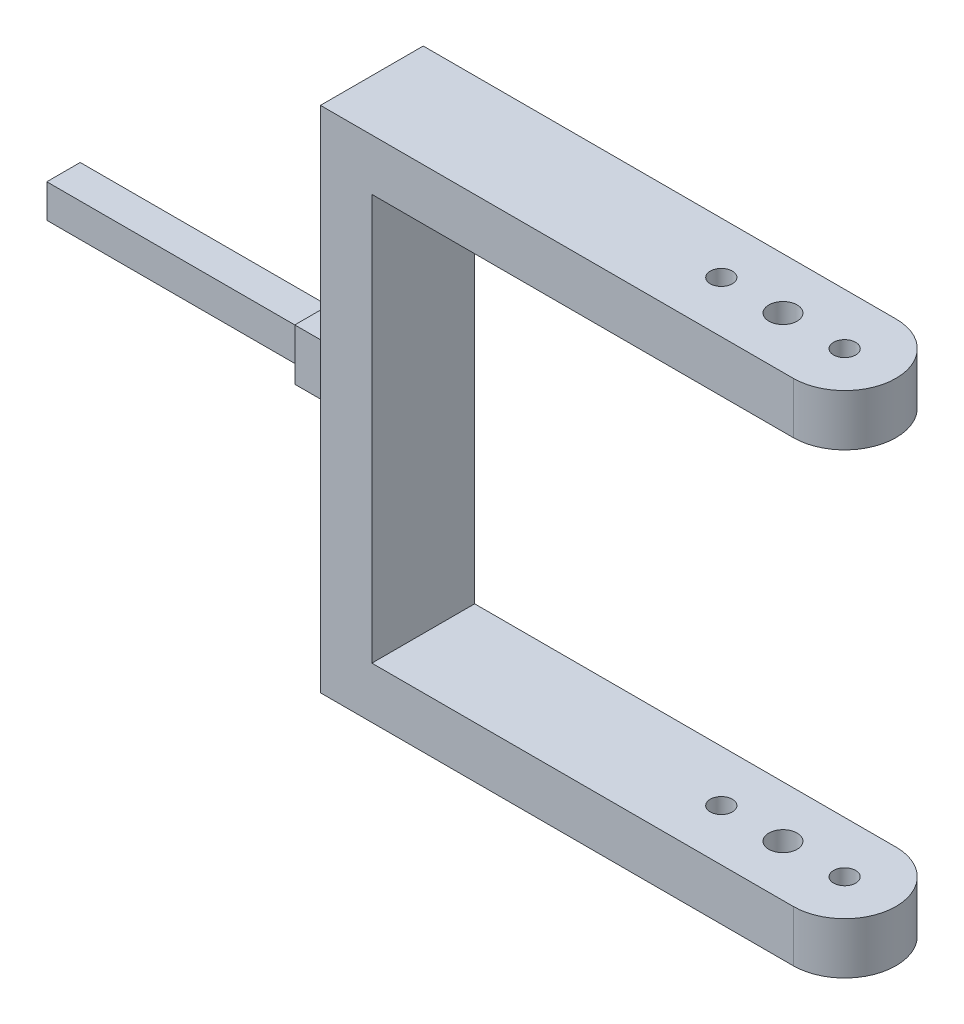
SolidWorks part; units mm, degrees
note: '?' marks a value the reader was unsure of. The reader was unsure of these and kept them because the rebuilt part matched: shared geometry of "草图3<3>".
ref_plane "前视基准面" through (0, 0, 0) normal (0, 0, 1) x (1, 0, 0)
ref_plane "上视基准面" through (0, 0, 0) normal (0, 1, 0) x (1, 0, 0)
ref_plane "右视基准面" through (0, 0, 0) normal (1, 0, 0) x (0, 0, -1)
other "Configuration Table"
sketch "草图1" plane through (0, 0, 0) normal (0, 0, 1) x (1, 0, 0)
  line L0 (0, 39.5) -> (0, -39.5)
  line L1 (0, 39.5) -> (80, 39.5)
  line L2 (80, 39.5) -> (80, 49.5)
  line L3 (80, 49.5) -> (-10, 49.5)
  line L4 (-10, 49.5) -> (-10, -49.5)
  line L5 (-10, -49.5) -> (80, -49.5)
  line L6 (80, -49.5) -> (80, -39.5)
  line L7 (80, -39.5) -> (0, -39.5)
  point P4 (0, 0)
  dimension "D1" = 79
  dimension "D2" = 80
  dimension "D3" = 10
  dimension "D4" = 10
  dimension "D5" = 10
extrude "凸台-拉伸1" add sketch "草图1" along normal blind 20
sketch "草图3" plane through (-10, 0, 0) normal (-1, 0, 0) x (0, 0, 1)
  line L0 (0, 49.5) -> (20, -49.5) construction
  line L1 (0, -49.5) -> (20, 49.5) construction
  line L2 (6.75, 3.25) -> (13.25, 3.25)
  line L3 (5, 5) -> (15, 5)
  line L4 (0, 49.5) -> (0, -49.5)
  line L5 (0, -49.5) -> (20, -49.5)
  line L6 (20, -49.5) -> (20, 49.5)
  line L7 (20, 49.5) -> (0, 49.5)
  line L8 (0, 49.5) -> (0, -49.5)
  line L9 (0, -49.5) -> (20, -49.5)
  line L10 (20, -49.5) -> (20, 49.5)
  line L11 (20, 49.5) -> (0, 49.5)
  line L12 (5, 5) -> (5, -5)
  line L13 (5, -5) -> (15, -5)
  line L14 (15, 5) -> (15, -5)
  line L15 (5, 5) -> (15, -5) construction
  line L16 (5, -5) -> (15, 5) construction
  line L17 (13.25, 3.25) -> (13.25, -3.25)
  line L18 (6.75, -3.25) -> (13.25, -3.25)
  line L19 (6.75, 3.25) -> (6.75, -3.25)
  point P4 (10, 0)
  point P5 (0, -49.5444)
  dimension "D2" = 10
  dimension "D3" = 1.75
  dimension "D1" = 0
extrude "凸台-拉伸2" add sketch "草图3" along normal blind 10 contours L14 L3 L12 L13 L19 L2 L17 L18 | L2 L19 L18 L17
extrude "凸台-拉伸3" add sketch "草图3<3>" along normal blind 50 from surface at 10 contours L2 L19 L18 L17 starting at face at (-20, 0, 10)
sketch "草图3<3>" plane through (-10, 0, 0) normal (-1, 0, 0) x (0, 0, 1) same geometry as "草图3"
sketch "草图4" plane through (80, 0, 0) normal (1, 0, 0) x (0, 0, -1)
  line L0 (0, -49.5) -> (0, -39.5) construction
  line L1 (0, -39.5) -> (-20, -39.5) construction
  line L2 (-20, -39.5) -> (-20, -49.5) construction
  line L3 (-20, -49.5) -> (0, -49.5) construction
  line L4 (0, 39.5) -> (0, 49.5) construction
  line L5 (0, 49.5) -> (-20, 49.5) construction
  line L6 (-20, 49.5) -> (-20, 39.5) construction
  line L7 (-20, 39.5) -> (0, 39.5) construction
  line L8 (0, -49.5) -> (0, -39.5)
  line L9 (0, -39.5) -> (-20, -39.5)
  line L10 (-20, -39.5) -> (-20, -49.5)
  line L11 (-20, -49.5) -> (0, -49.5)
  line L12 (0, 39.5) -> (0, 49.5)
  line L13 (0, 49.5) -> (-20, 49.5)
  line L14 (-20, 49.5) -> (-20, 39.5)
  line L15 (-20, 39.5) -> (0, 39.5)
extrude "凸台-拉伸4" add sketch "草图4" along normal blind 12
sketch "草图2" plane through (0, 49.5, 0) normal (0, 1, 0) x (1, 0, 0)
  line L0 (-10, -10) -> (92, -10) construction
  line L1 (-10, -20) -> (-10, 0) construction
  line L4 (92, 0) -> (92, -20) construction
  line L5 (92, 0) -> (-10, 0) construction
  circle A1 centre (70, -10) radius 2.75
  circle A2 centre (82, -10) radius 10
  circle A4 centre (58, -10) radius 2.15
  circle A5 centre (82, -10) radius 2.15
  line M1 (92, 0) -> (-10, 0)
  line M3 (-10, -20) -> (92, -20)
  line M11 (92, -20) -> (92, 0)
  dimension "D1" = 5.5
  dimension "D3" = 4.3
  dimension "D4" = 4.3
  dimension "D5" = 12
  dimension "D2" = 80
  dimension "D6" = 12
extrude "切除-拉伸1" cut sketch "草图2" against normal through all contours A1 L0 | L0 A1 | A1 L0 A2 | L0 A1 A2 | L0 A2 A1 | A2 L0 A1 | A5 L0 | L0 A5 | A2 M11 M1 | A2 M3 M11
ref_plane "基准面1" through (0, 0, 10) normal (0, 0, 1) x (1, 0, 0)
ref_axis "基准轴1" through (-20, -5, 10) along (0, 1, 0)?
